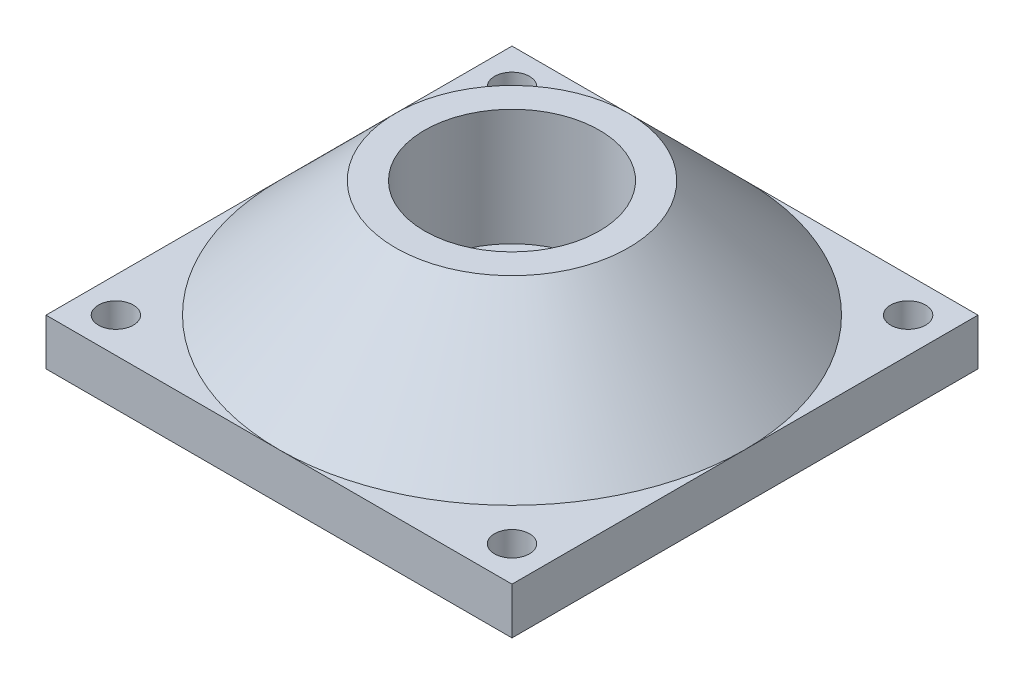
SolidWorks part; units mm, degrees
ref_plane "Ebene vorne" through (0, 0, 0) normal (0, 0, 1) x (1, 0, 0)
ref_plane "Ebene oben" through (0, 0, 0) normal (0, 1, 0) x (1, 0, 0)
ref_plane "Ebene rechts" through (0, 0, 0) normal (1, 0, 0) x (0, 0, -1)
sketch "Skizze1" plane through (0, 0, 0) normal (0, 1, 0) x (1, 0, 0)
  line L1 (-100, -100) -> (100, -100)
  line L2 (-100, -100) -> (-100, 100)
  line L3 (-100, 100) -> (100, 100)
  line L4 (100, -100) -> (100, 100)
  line L5 (-100, -100) -> (100, 100) construction
  line L6 (-100, 100) -> (100, -100) construction
  point P0 (0, 0)
  point P6 (-100, -6.5208)
  dimension "D1" = 200
  dimension "D2" = 200
extrude "Aufsatz-Linear austragen1" add sketch "Skizze1" along normal blind 20
sketch "Skizze2" plane through (0, 20, 0) normal (0, 1, 0) x (1, 0, 0)
  circle A0 centre (0, 0) radius 37.5
  circle A1 centre (0, 0) radius 50
extrude "Aufsatz-Linear austragen2" add sketch "Skizze2" along normal blind 50
chamfer "Fase1" distance 50 angle 45 1 edges at (0, 20, -50)
sketch "Skizze3" plane through (0, 20, 0) normal (0, 1, 0) x (1, 0, 0)
  line L0 (100, 100) -> (0, 100) construction
  line L1 (100, 0) -> (100, 100) construction
  line L2 (0, -38.5) -> (0, 38.5) construction
  line L3 (-38.5, 0) -> (38.5, 0) construction
  circle A0 centre (85, 85) radius 7.5
  circle A1 centre (-85, 85) radius 7.5
  circle A2 centre (85, -85) radius 7.5
  circle A3 centre (-85, -85) radius 7.5
  dimension "D3" = 15
  dimension "D1" = 15
  dimension "D2" = 15
extrude "Schnitt-Linear austragen1" cut sketch "Skizze3" against normal blind 50
